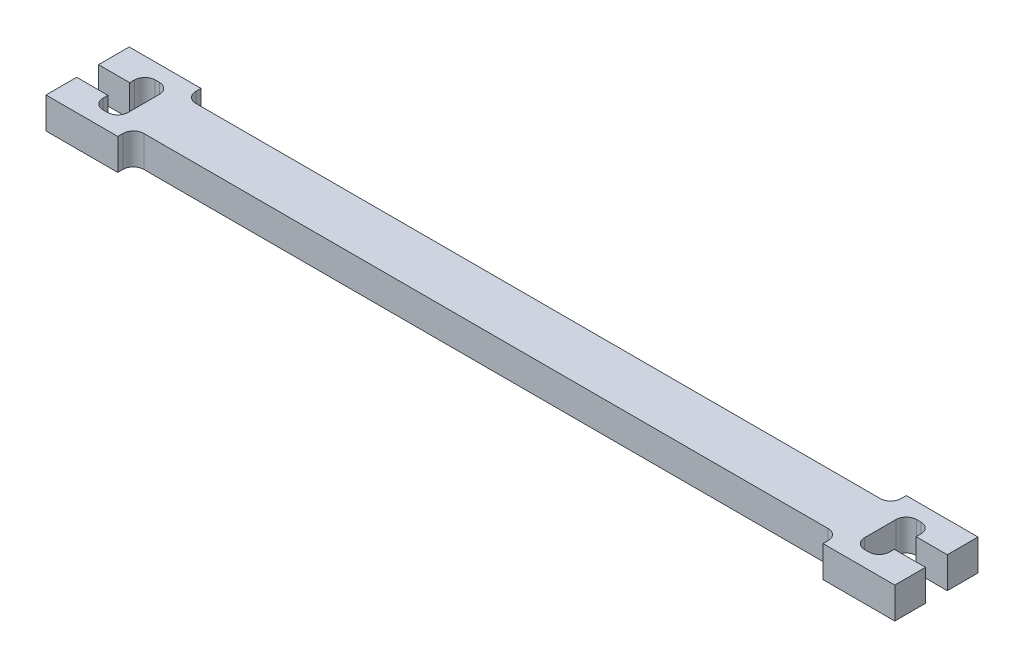
SolidWorks part; units mm, degrees
ref_plane "Front Plane" through (0, 0, 0) normal (0, 0, 1) x (1, 0, 0)
ref_plane "Top Plane" through (0, 0, 0) normal (0, 1, 0) x (1, 0, 0)
ref_plane "Right Plane" through (0, 0, 0) normal (1, 0, 0) x (0, 0, -1)
sketch "Sketch1" plane through (0, 0, 0) normal (0, 1, 0) x (1, 0, 0)
  line L0 (-40.8, 0) -> (40.8, 0) construction
  line L1 (-40.8, 4) -> (40.8, 4)
  line L2 (-40.8, 4) -> (-40.8, -4)
  line L3 (-40.8, -4) -> (40.8, -4)
  line L4 (40.8, 4) -> (40.8, -4)
  line L5 (-40.8, 4) -> (40.8, -4) construction
  line L6 (-40.8, -4) -> (40.8, 4) construction
  line L7 (-35.4, 2.5) -> (-35.4, 4) construction
  line L8 (-40.8, 1.05) -> (-37.8, 1.05)
  line L9 (-40.8, 1.05) -> (-40.8, -1.05)
  line L10 (-40.8, -1.05) -> (-37.8, -1.05)
  line L11 (-37.8, 1.05) -> (-37.8, -1.05)
  line L12 (-40.8, 1.05) -> (-37.8, -1.05) construction
  line L13 (-40.8, -1.05) -> (-37.8, 1.05) construction
  line L14 (-37.8, 2.5) -> (-35.4, 2.5)
  line L15 (-37.8, 2.5) -> (-37.8, -2.5)
  line L16 (-37.8, -2.5) -> (-35.4, -2.5)
  line L17 (-35.4, 2.5) -> (-35.4, -2.5)
  line L18 (-37.8, 2.5) -> (-35.4, -2.5) construction
  line L19 (-37.8, -2.5) -> (-35.4, 2.5) construction
  line L20 (-33.9, 2.5) -> (33.9, 2.5)
  line L21 (-33.9, 2.5) -> (-33.9, -2.5)
  line L22 (-33.9, -2.5) -> (33.9, -2.5)
  line L23 (33.9, 2.5) -> (33.9, -2.5)
  line L24 (-33.9, 2.5) -> (33.9, -2.5) construction
  line L25 (-33.9, -2.5) -> (33.9, 2.5) construction
  line L26 (-35.4, 2.5) -> (-33.9, 2.5) construction
  line L27 (-33.9, 2.5) -> (-33.9, 4)
  line L28 (-33.9, -2.5) -> (-33.9, -4)
  line L29 (0, 4) -> (0, -4) construction
  line L30 (33.9, -2.5) -> (33.9, -4)
  line L31 (-40.8, 4) -> (-40.8, -4)
  line L32 (40.8, 4) -> (40.8, -4)
  line L33 (33.9, 2.5) -> (33.9, 4)
  line L34 (40.8, -1.05) -> (37.8, -1.05)
  line L35 (37.8, -2.5) -> (35.4, -2.5)
  line L36 (35.4, 2.5) -> (35.4, -2.5)
  line L37 (37.8, 2.5) -> (35.4, 2.5)
  line L38 (37.8, 2.5) -> (37.8, -2.5)
  line L39 (40.8, 1.05) -> (37.8, 1.05)
  point P0 (0, 0)
  point P8 (-39.3, 0)
  point P13 (-36.6, 0)
  point P18 (0, 0)
  point P38 (0, -4)
  dimension "D1" = 8
  dimension "D2" = 81.6
  dimension "D3" = 3
  dimension "D4" = 2.4
  dimension "D5" = 5
  dimension "D6" = 2.1
extrude "Base shape" add sketch "Sketch1" along normal blind 3 contours L23 L20 L21 L22 | L28 L21 L27 L1 L2 L8 L15 L14 L17 L16 L10 L3 | L39 L4 L1 L33 L23 L30 L3 L32 L34 L38 L35 L36 L37 region at (-37.35, 0, -3.8944) region at (37.35, 0, -3.8944) region at (0, 0, 0)
fillet "Milling fillets" radius 1 12 edges at (37.8, 1.5, 2.5) (-35.4, 1.5, 2.5) (-37.8, 1.5, 2.5) (35.4, 1.5, 2.5) (35.4, 1.5, -2.5) (-37.8, 1.5, -2.5) (-35.4, 1.5, -2.5) (37.8, 1.5, -2.5) (33.9, 1.5, 2.5) (33.9, 1.5, -2.5) (-33.9, 1.5, -2.5) (-33.9, 1.5, 2.5)
sketch "Center axis sketch" plane through (40.8, 0, 0) normal (1, 0, 0) x (0, 0, -1)
  line L0 (-1.05, 0) -> (1.05, 3) construction
  point P4 (0, 1.5)
ref_axis "Center axis" through (-46.4653, 1.5, 0) along (1, 0, 0)
